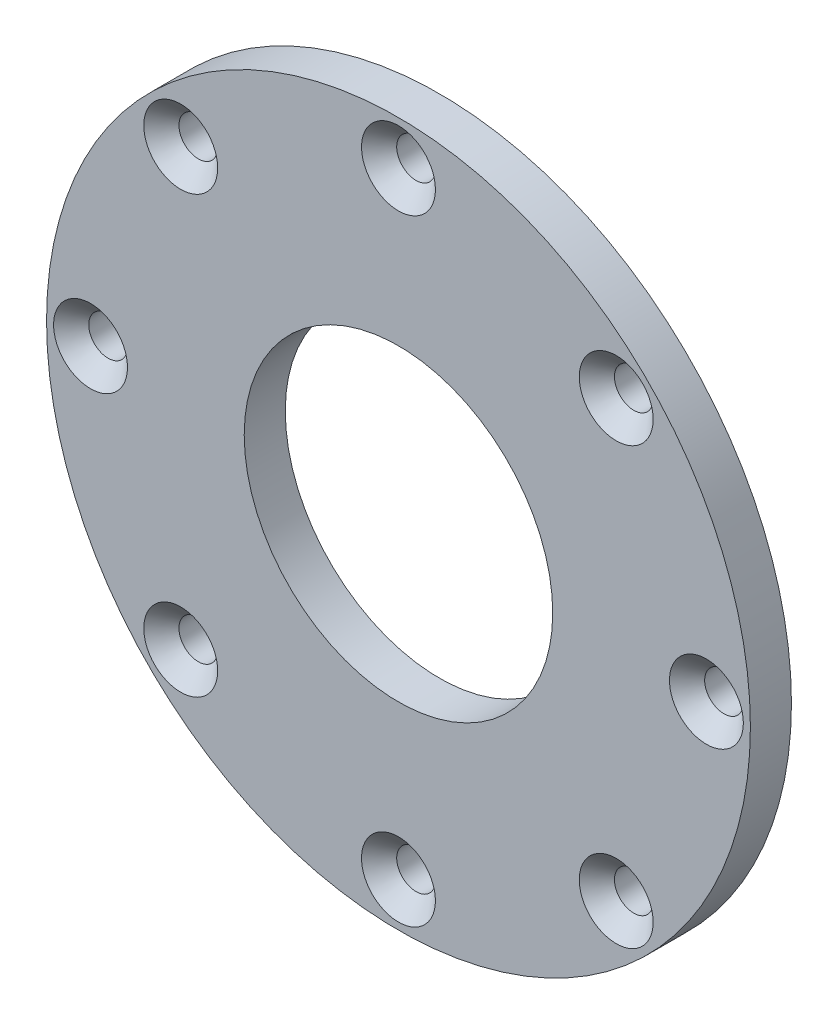
SolidWorks part; units mm, degrees
material "Polylactic Acid (PLA)"
ref_plane "Front Plane" through (0, 0, 0) normal (0, 0, 1) x (1, 0, 0)
ref_plane "Top Plane" through (0, 0, 0) normal (0, 1, 0) x (1, 0, 0)
ref_plane "Right Plane" through (0, 0, 0) normal (1, 0, 0) x (0, 0, -1)
sketch "Sketch1" plane through (0, 0, 0) normal (0, 0, 1) x (1, 0, 0)
  circle A0 centre (0, 0) radius 60
  circle A1 centre (0, 0) radius 26.3
  dimension "D1" = 120
  dimension "D2" = 52.6
extrude "Boss-Extrude1" add sketch "Sketch1" along normal blind 7
sketch "Sketch2" plane through (0, 0, 7) normal (0, 0, 1) x (1, 0, 0)
  circle A0 centre (0, 0) radius 52.5
  circle A1 centre (0, 0) radius 60 construction
  point P5 (0, 52.5)
  point P8 (37.1231, 37.1231)
  point P9 (52.5, 0)
  point P10 (37.1231, -37.1231)
  point P11 (0, -52.5)
  point P12 (-37.1231, -37.1231)
  point P13 (-52.5, 0)
  point P14 (-37.1231, 37.1231)
  dimension "D1" = 7.5
  dimension "D2" = 8
hole_wizard "CSK for M6 Countersunk Flat Head Screw1" positions "Sketch2" profile "Sketch3" countersink size "M6" standard "ISO" end condition through all
sketch "Sketch3" plane through (-37.1231, 37.1231, 7) normal (1, 0, 0) x (0, -1, 0)
  line L0 (0, 0) -> (0, 7)
  line L1 (0, 7) -> (3.3, 7)
  line L2 (3.3, 7) -> (3.3, 3)
  line L3 (3.3, 3) -> (6.3, 0)
  line L5 (6.3, 0) -> (0, 0)
  line L6 (-3.3, 3) -> (-6.3, 0) construction
  line L11 (0, -6.35) -> (0, 107.95) construction
  dimension "Thru Hole Dia." = 6.6
  dimension "Thru Hole Depth" = 7
  dimension "Near C'Sink Dia." = 12.6
  dimension "Near C'Sink Angle" = 90
